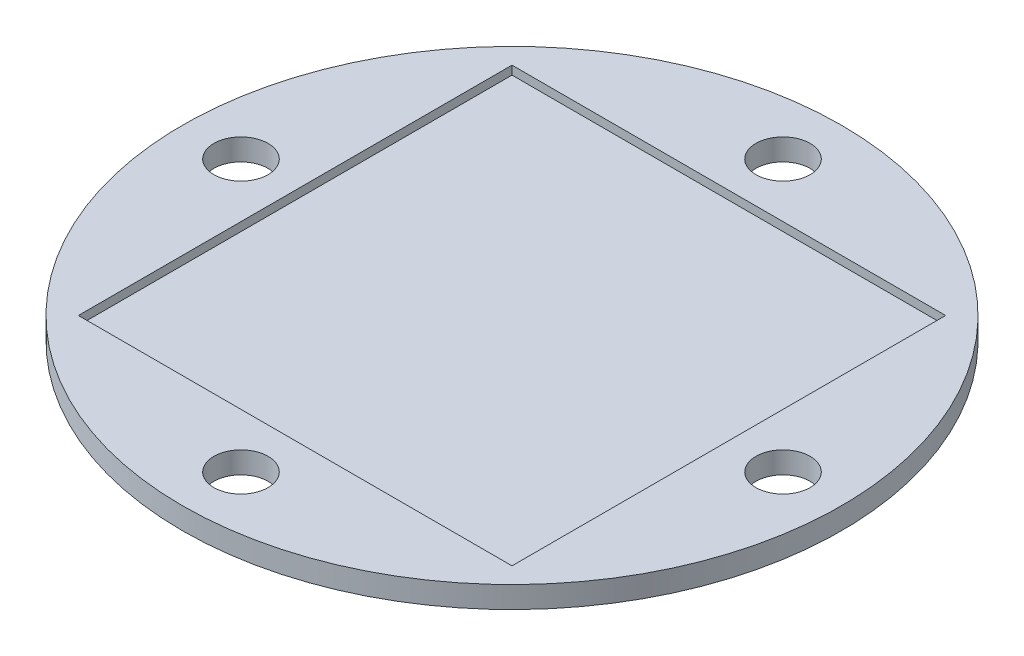
SolidWorks part; units mm, degrees
material "Custom Plastic"
ref_plane "Front Plane" through (0, 0, 0) normal (0, 0, 1) x (1, 0, 0)
ref_plane "Top Plane" through (0, 0, 0) normal (0, 1, 0) x (1, 0, 0)
ref_plane "Right Plane" through (0, 0, 0) normal (1, 0, 0) x (0, 0, -1)
sketch "Sketch1" plane through (0, 0, 0) normal (0, 1, 0) x (1, 0, 0)
  line L0 (0, 0) -> (0, -17.9724) construction
  line L1 (-50, -50) -> (50, -50)
  line L2 (-50, -50) -> (-50, 50)
  line L3 (-50, 50) -> (50, 50)
  line L4 (50, -50) -> (50, 50)
  line L5 (-50, -50) -> (50, 50) construction
  line L6 (-50, 50) -> (50, -50) construction
  line L7 (0, 0) -> (14.9739, 0) construction
  line L8 (0, 62.5) -> (14.3316, 62.5) construction
  line L9 (0, 76) -> (25.822, 76) construction
  circle A0 centre (0, 0) radius 76
  circle A1 centre (0, 0) radius 62.5 construction
  circle A2 centre (0, 62.5) radius 6.25
  circle A3 centre (62.5, 0) radius 6.25
  circle A4 centre (0, -62.5) radius 6.25
  circle A5 centre (-62.5, 0) radius 6.25
  dimension "D1" = 152
  dimension "D4" = 125
  dimension "D5" = 12.5
  dimension "D2" = 100
  dimension "D3" = 100
extrude "Boss-Extrude1" add sketch "Sketch1" along normal blind 5 contours L2 L1 L4 L3 | A0
sketch "Sketch3" plane through (0, 5, 0) normal (0, 1, 0) x (1, 0, 0)
  line L1 (-50, -50) -> (50, -50)
  line L2 (-50, -50) -> (-50, 50)
  line L3 (-50, 50) -> (50, 50)
  line L4 (50, -50) -> (50, 50)
  line L5 (-50, -50) -> (50, 50) construction
  line L6 (-50, 50) -> (50, -50) construction
  point P0 (0, 0)
extrude "Boss-Extrude2" add sketch "Sketch3" against normal blind 5
extrude "Cut-Extrude1" cut sketch "Sketch3<2>" against normal blind 2
sketch "Sketch3<2>" plane through (0, 5, 0) normal (0, 1, 0) x (1, 0, 0) same geometry as "Sketch3"
sketch "Sketch6" plane through (0, 5, 0) normal (0, 1, 0) x (1, 0, 0)
  circle A0 centre (0, 0) radius 62.5 construction
  circle A1 centre (0, 62.5) radius 6.25
  circle A2 centre (62.5, 0) radius 6.25
  circle A3 centre (0, -62.5) radius 6.25
  circle A4 centre (-62.5, 0) radius 6.25
  dimension "D1" = 125
  dimension "D2" = 12.5
extrude "Cut-Extrude2" cut sketch "Sketch6" against normal blind 10
